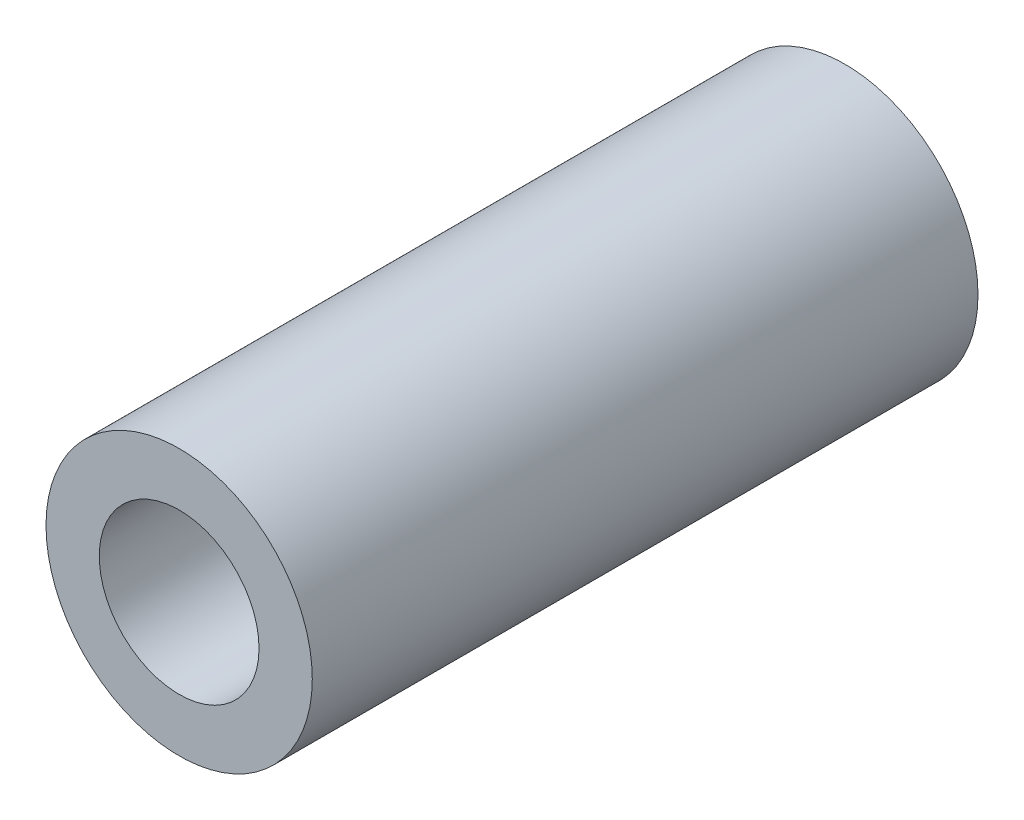
SolidWorks part; units mm, degrees
material "Copper"
ref_plane "Front Plane" through (0, 0, 0) normal (0, 0, 1) x (1, 0, 0)
ref_plane "Top Plane" through (0, 0, 0) normal (0, 1, 0) x (1, 0, 0)
ref_plane "Right Plane" through (0, 0, 0) normal (1, 0, 0) x (0, 0, -1)
sketch "Sketch1" plane through (0, 0, 0) normal (0, 0, 1) x (1, 0, 0)
  circle A0 centre (0, 0) radius 6
  circle A1 centre (0, 0) radius 10
  dimension "D1" = 12
  dimension "D2" = 20
extrude "Boss-Extrude1" add sketch "Sketch1" along normal blind 50
